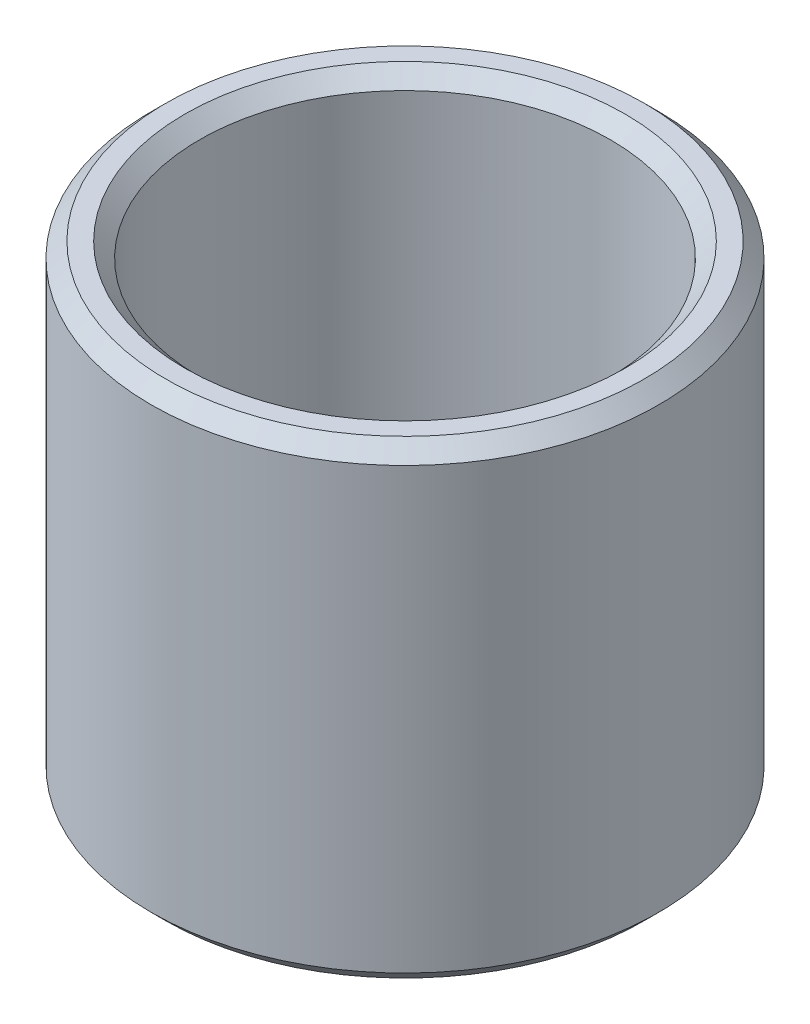
SolidWorks part; units mm, degrees
ref_plane "Front Plane" through (0, 0, 0) normal (0, 0, 1) x (1, 0, 0)
ref_plane "Top Plane" through (0, 0, 0) normal (0, 1, 0) x (1, 0, 0)
ref_plane "Right Plane" through (0, 0, 0) normal (1, 0, 0) x (0, 0, -1)
sketch "Sketch1" plane through (0, 0, 0) normal (0, 1, 0) x (1, 0, 0)
  circle A0 centre (0, 0) radius 60
  dimension "SLEEVE_OD" = 120
extrude "Boss-Extrude1" add sketch "Sketch1" along normal blind 110.8726
sketch "Sketch2" plane through (0, 0, 0) normal (0, 1, 0) x (1, 0, 0)
  circle A0 centre (0, 0) radius 48.5346
  dimension "BORE_D" = 97.0692
extrude "Cut-Extrude1" cut sketch "Sketch2" along normal through all
chamfer "Chamfer1" distance 3.4974 angle 45 4 edges at (0, 110.8726, 48.5346) (0, 0, 48.5346) (0, 0, 60) (0, 110.8726, 60)
